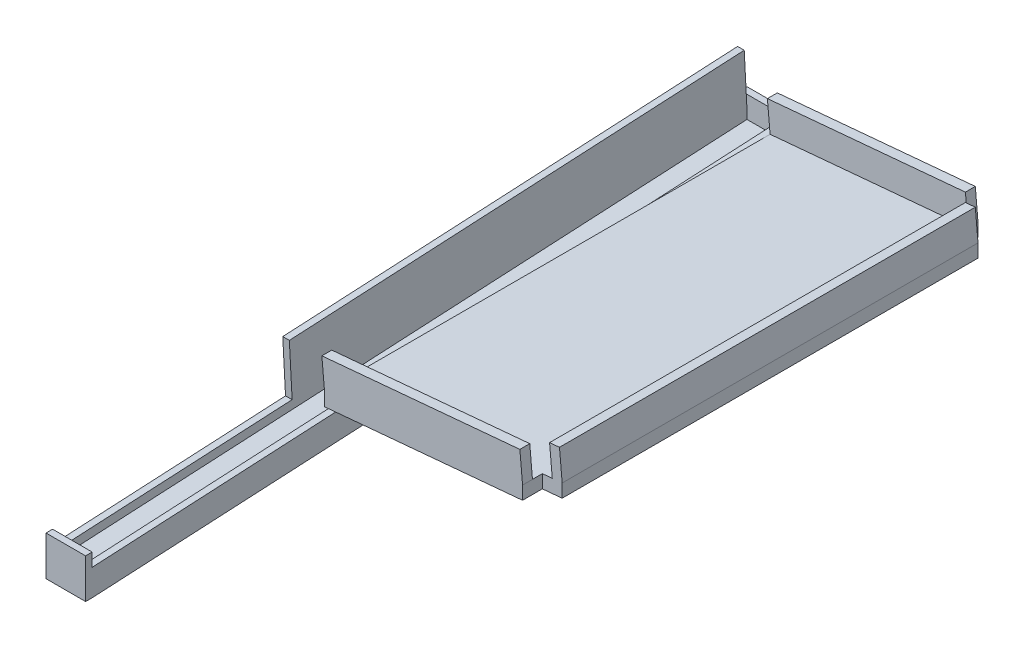
SolidWorks part; units mm, degrees
ref_plane "Front Plane" through (0, 0, 0) normal (0, 0, 1) x (1, 0, 0)
ref_plane "Top Plane" through (0, 0, 0) normal (0, 1, 0) x (1, 0, 0)
ref_plane "Right Plane" through (0, 0, 0) normal (1, 0, 0) x (0, 0, -1)
sketch "Sketch1" plane through (0, 0, 0) normal (0, 0, 1) x (1, 0, 0)
  line L0 (0, 0) -> (0, 20)
  line L1 (0, 0) -> (330, 0)
  line L2 (330, 0) -> (330, 50)
  line L3 (330, 50) -> (0, 20)
  line L4 (0, 0) -> (330, 30)
  dimension "D1" = 20
  dimension "D2" = 20
  dimension "D3" = 330
  dimension "D4" = 50
extrude "Boss-Extrude1" add sketch "Sketch1" along normal blind 690 contours L0 L4 L2 L3 region at (165, 25, 0)
sketch "Sketch3" plane through (0, 0, 0) normal (0, 1, 0) x (1, 0, 0)
  line L0 (300, -690) -> (330, -690)
  line L1 (330, -690) -> (330, -660)
  line L2 (330, -30) -> (330, 0)
  line L3 (330, -690) -> (300, -690)
  line L4 (330, -690) -> (330, -660)
  line L5 (330, -660) -> (300, -660)
  line L6 (300, -690) -> (300, -660)
  line L7 (330, 0) -> (300, 0)
  line L8 (330, 0) -> (330, -30)
  line L9 (330, -30) -> (300, -30)
  line L10 (300, 0) -> (300, -30)
  dimension "D2" = 30
  dimension "D3" = 30
  dimension "D4" = 30
  dimension "D5" = 30
  dimension "D6" = 690
extrude "Cut-Extrude2" cut sketch "Sketch3" along normal through all contours L6 L0 L1 L5 | L7 L10 L9 L2 region at (315, 0, 675) region at (315, 0, 15)
sketch "Sketch4" plane through (0, 0, 0) normal (-1, 0, 0) x (0, 0, 1)
  line L0 (0, 20) -> (0, 0)
  line L1 (1042, -34.6089) -> (1042, -54.6089)
  line L3 (0, 20) -> (1042, -34.6089)
  line L4 (1042, -54.6089) -> (1042, -74.6089)
  line L5 (1042, -74.6089) -> (0, -20)
  line L6 (0, -20) -> (0, 0)
  dimension "D1" = 40
  dimension "D2" = 20
  dimension "D3" = 40
  dimension "D4" = 87
  dimension "D5" = 1042
extrude "Boss-Extrude2" add sketch "Sketch4" along normal blind 60
sketch "Sketch6" plane through (0, 19.9452, 1.0453) normal (0, 0.9986, 0.0523) x (1, 0, 0)
  line L1 (-60, 1.0467) -> (0, 1.0467) construction
  line L2 (-50, 1.0467) -> (-50, -1042.3833)
  line L3 (-60, -1042.3833) -> (0, -1042.3833) construction
  line L4 (-50, -1042.3833) -> (-10, -1042.3833)
  line L5 (-10, -1042.3833) -> (-10, 1.0467)
  line L6 (-10, 1.0467) -> (-50, 1.0467)
  dimension "D1" = 10
  dimension "D2" = 10
extrude "Cut-Extrude3" cut sketch "Sketch6" against normal blind 13
sketch "Sketch7" plane through (0, -54.5541, 1040.9547) normal (0, 0.0523, -0.9986) x (-1, 0, 0)
  line L0 (10, 6.9726) -> (10, 19.9726)
  line L1 (10, 19.9726) -> (50, 19.9726)
  line L2 (50, 19.9726) -> (50, 6.9726)
  line L3 (50, 6.9726) -> (10, 6.9726)
extrude "Cut-Extrude4" cut sketch "Sketch7" against normal through all
sketch "Sketch8" plane through (0, 19.9452, 1.0453) normal (0, 0.9986, 0.0523) x (1, 0, 0)
  line L1 (-60, 1.0467) -> (-50, 1.0467)
  line L2 (-60, 1.0467) -> (-60, -689.0232)
  line L3 (-60, -689.0232) -> (-50, -689.0232)
  line L4 (-50, 1.0467) -> (-50, -689.0232)
  dimension "D1" = 690.0699
sketch "Sketch10" plane through (0, 0, 1042) normal (0, 0, 1) x (1, 0, 0)
  line L10 (-60, -14.6089) -> (0, -14.6089)
  line L11 (-60, -14.6089) -> (-60, -74.6089)
  line L12 (-60, -74.6089) -> (0, -74.6089)
  line L13 (0, -14.6089) -> (0, -74.6089)
  dimension "D1" = 60
extrude "Boss-Extrude4" add sketch "Sketch10" along normal blind 10
ref_plane "Plane1" through (0, -80, 0) normal (0, 1, 0) x (1, 0, 0)
sketch "Sketch16" plane through (-60, 0, 0) normal (-1, 0, 0) x (0, 0, 1)
  line L0 (0, -20) -> (0, -80)
  line L1 (214.5, -80) -> (-214.5, -80) construction
  line L2 (0, -80) -> (30, -80)
  line L3 (30, -80) -> (30, -21.5722)
  line L4 (0, -20) -> (1042, -74.6089) construction
  line L5 (521, -47.3045) -> (521, -80)
  line L6 (521, -80) -> (551, -80)
  line L7 (551, -80) -> (551, -48.8767)
  line L8 (521, -47.3045) -> (551, -48.8767)
  line L9 (0, -20) -> (30, -21.5722)
  dimension "D1" = 30
  dimension "D2" = 30
extrude "Boss-Extrude8" add sketch "Sketch16" against normal blind 30
sketch "Sketch17" plane through (-1.8033, 19.8361, 0) normal (-0.0905, 0.9959, 0) x (0.9959, 0.0905, 0)
  line L0 (1.8107, -690) -> (1.8107, 0) construction
  line L1 (1.8107, -15) -> (303.0478, -15)
  line L2 (1.8107, -15) -> (1.8107, 0)
  line L3 (1.8107, 0) -> (303.0478, 0)
  line L4 (303.0478, -15) -> (303.0478, 0)
  line L6 (333.1715, -30) -> (318.1097, -30)
  line L7 (333.1715, -30) -> (333.1715, -660)
  line L8 (333.1715, -660) -> (318.1097, -660)
  line L9 (318.1097, -30) -> (318.1097, -660)
  line L10 (303.0478, -690) -> (303.0478, -660) construction
  line L11 (303.0478, -675) -> (1.8107, -675)
  line L12 (303.0478, -675) -> (303.0478, -690)
  line L13 (303.0478, -690) -> (1.8107, -690)
  line L14 (1.8107, -675) -> (1.8107, -690)
  line L15 (303.0478, 0) -> (303.0478, -30) construction
  line L17 (333.1715, -30) -> (303.0478, -30) construction
  point P35 (318.1097, -30)
extrude "Boss-Extrude9" add sketch "Sketch17" along normal blind 45
extrude "Boss-Extrude10" add sketch "Sketch8" along normal blind 80 contours L4 L3 L2 L1
sketch "Sketch21" plane through (0, 0, 0) normal (0, 0, -1) x (-1, 0, 0)
  line L0 (60, 99.8904) -> (60, 20) construction
  line L1 (0, -20) -> (60, -20)
  line L2 (0, -20) -> (0, 40)
  line L3 (0, 40) -> (60, 40)
  line L4 (60, -20) -> (60, 40)
  dimension "D1" = 60
extrude "Boss-Extrude14" add sketch "Sketch21" along normal blind 10 separate body
